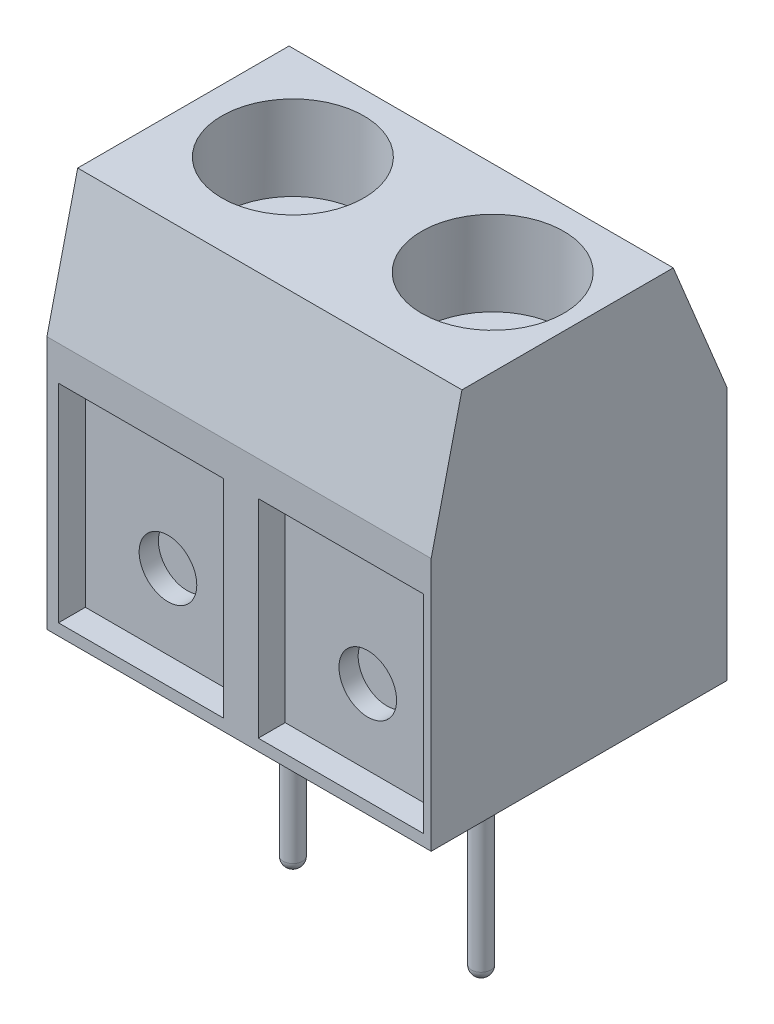
SolidWorks part; units mm, degrees
ref_plane "Alzado" through (0, 0, 0) normal (0, 0, 1) x (1, 0, 0)
ref_plane "Planta" through (0, 0, 0) normal (0, 1, 0) x (1, 0, 0)
ref_plane "Vista lateral" through (0, 0, 0) normal (1, 0, 0) x (0, 0, -1)
sketch "Croquis1" plane through (0, 0, 0) normal (0, 1, 0) x (1, 0, 0)
  line L1 (-5, 3.85) -> (5, 3.85)
  line L2 (-5, 3.85) -> (-5, -3.85)
  line L3 (-5, -3.85) -> (5, -3.85)
  line L4 (5, 3.85) -> (5, -3.85)
  line L5 (-5, 3.85) -> (5, -3.85) construction
  line L6 (-5, -3.85) -> (5, 3.85) construction
  point P0 (0, 0)
  dimension "D1" = 10
  dimension "D2" = 7.7
extrude "Saliente-Extruir1" add sketch "Croquis1" along normal blind 6.6
sketch "Croquis2" plane through (0, 0, 0) normal (1, 0, 0) x (0, 0, -1)
  line L0 (-3.85, 6.6) -> (3.85, 6.6) construction
  line L1 (-3.85, 6.6) -> (3.85, 6.6)
  line L2 (-3.05, 10) -> (2.45, 10)
  line L3 (2.45, 10) -> (3.85, 6.6)
  line L4 (-3.85, 6.6) -> (-3.05, 10)
  line L6 (-3.85, 0) -> (3.85, 0) construction
  dimension "D1" = 10
  dimension "D2" = 0.8
  dimension "D3" = 5.5
extrude "Saliente-Extruir2" add sketch "Croquis2" along normal up to surface and the other way up to surface up to face at (5, 3.3, 0) other way up to face at (-5, 3.3, 0)
sketch "Croquis3" plane through (0, 10, 0) normal (0, 1, 0) x (1, 0, 0)
  line L0 (-5, -3.05) -> (-5, 2.45) construction
  circle A0 centre (-2.45, 0) radius 1.85
  dimension "D1" = 3.7
  dimension "D2" = 2.55
extrude "Cortar-Extruir1" cut sketch "Croquis3" against normal blind 2.2
sketch "Croquis4" plane through (0, 7.8, 0) normal (0, 1, 0) x (1, 0, 0)
  line L0 (-2.45, -1.85) -> (-2.45, 1.85) construction
  line L1 (-4.3, 0) -> (-0.6, 0) construction
  line L2 (-2.2, -1.85) -> (-2.2, -0.25)
  line L3 (-4.3, -0.25) -> (-2.7, -0.25)
  line L4 (-2.7, -1.85) -> (-2.7, -0.25)
  line L5 (-4.3, 0.25) -> (-2.7, 0.25)
  line L6 (-2.2, 0.25) -> (-0.6, 0.25)
  line L7 (-4.3, 0.25) -> (-0.6, 0.25) construction
  line L8 (-2.2, 0.25) -> (-2.2, 1.85)
  line L9 (-2.2, -1.85) -> (-2.2, 1.85) construction
  line L10 (-2.2, -0.25) -> (-0.6, -0.25)
  line L11 (-4.3, -0.25) -> (-0.6, -0.25) construction
  line L12 (-2.7, 0.25) -> (-2.7, 1.85)
  line L13 (-2.7, -1.85) -> (-2.7, 1.85) construction
  circle A1 centre (-2.45, 0) radius 1.85
  circle A2 centre (-2.45, 0) radius 1.85
  circle M4 centre (-2.45, 0) radius 1.85
  dimension "D1" = 0
  dimension "D2" = 0.25
  dimension "D3" = 0.25
extrude "Cortar-Extruir2" cut sketch "Croquis4" against normal blind 0.25 contours L12 L5 L3 L4 L2 L10 L6 L8 M4 region at (-2.45, 7.8, 0)
pattern_linear "MatrizL1" count 2 spacing 5.2 along (1, 0, 0) of "Cortar-Extruir1", "Cortar-Extruir2"
sketch "Croquis5" plane through (0, 0, 3.85) normal (0, 0, 1) x (1, 0, 0)
  line L1 (-4.7, 5.7) -> (-0.4, 5.7)
  line L2 (-4.7, 5.7) -> (-4.7, 0.3)
  line L3 (-4.7, 0.3) -> (-0.4, 0.3)
  line L4 (-0.4, 5.7) -> (-0.4, 0.3)
  line L5 (-4.7, 5.7) -> (-0.4, 0.3) construction
  line L6 (-4.7, 0.3) -> (-0.4, 5.7) construction
  line L8 (-5, 6.6) -> (-5, 0) construction
  line L9 (-5, 0) -> (5, 0) construction
  circle A0 centre (-2.55, 2.25) radius 0.75
  point P0 (-2.55, 3)
  dimension "D5" = 1.5
  dimension "D1" = 5.4
  dimension "D2" = 4.3
  dimension "D3" = 0.3
  dimension "D4" = 0.3
extrude "Cortar-Extruir3" cut sketch "Croquis5" against normal blind 0.7
extrude "Cortar-Extruir4" cut sketch "Croquis5<2>" against normal blind 1.2 contours A0 region at (-2.55, 2.25, 3.85)
sketch "Croquis5<2>" plane through (0, 0, 3.85) normal (0, 0, 1) x (1, 0, 0) same geometry as "Croquis5"
pattern_linear "MatrizL2" count 2 spacing 5.2 along (1, 0, 0) of "Cortar-Extruir4", "Cortar-Extruir3"
sketch "Croquis6" plane through (0, 0, 0) normal (0, -1, 0) x (1, 0, 0)
  line L4 (5, -3.85) -> (5, 3.85)
  line L5 (5, 3.85) -> (-5, 3.85)
  line L6 (-5, 3.85) -> (-5, -3.85)
  line L7 (-5, -3.85) -> (5, -3.85)
  line L8 (5, -3.85) -> (5, 3.85)
  line L9 (5, 3.85) -> (-5, 3.85)
  line L10 (-5, 3.85) -> (-5, -3.85)
  line L11 (-5, -3.85) -> (5, -3.85)
  circle A4 centre (-2.45, 0) radius 0.25
  circle A5 centre (2.45, 0) radius 0.25
  dimension "D2" = 0.5
  dimension "D4" = 2.45
  dimension "D5" = 2.45
  dimension "D1" = 0
  dimension "D3" = 2
extrude "Saliente-Extruir3" add sketch "Croquis6" along normal blind 6 contours A5 | A4 region at (-2.45, 0, 0) region at (2.45, 0, 0)
fillet "Redondeo1" radius 0.25 2 edges at (-2.45, -6, -0.25) (2.45, -6, -0.25)
